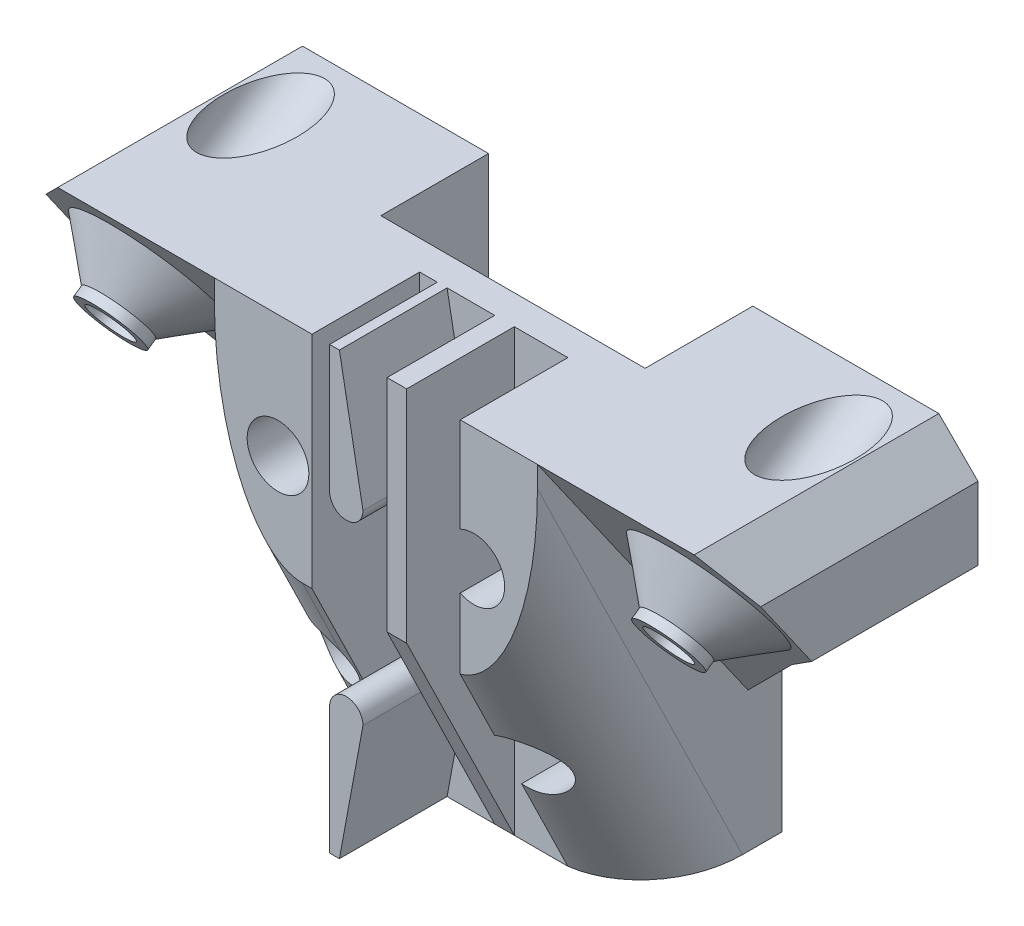
SolidWorks part; units mm, degrees
other "Markup1"
sketch "Sketch5" plane through (36.5, -22.5, 25) normal (0.516, -0.1626, 0.841) x (0.8506, -0.0189, -0.5255)
ref_plane "Front Plane" through (0, 0, 0) normal (0, 0, 1) x (1, 0, 0)
ref_plane "Top Plane" through (0, 0, 0) normal (0, 1, 0) x (1, 0, 0)
ref_plane "Right Plane" through (0, 0, 0) normal (1, 0, 0) x (0, 0, -1)
sketch "Sketch1" plane through (0, 0, 0) normal (0, 0, 1) x (1, 0, 0)
  line L1 (-16.5, -22.5) -> (16.5, -22.5)
  line L2 (-16.5, -22.5) -> (-16.5, 22.5)
  line L3 (-16.5, 22.5) -> (16.5, 22.5)
  line L4 (16.5, -22.5) -> (16.5, 22.5)
  line L5 (-16.5, -22.5) -> (16.5, 22.5) construction
  line L6 (-16.5, 22.5) -> (16.5, -22.5) construction
  point P0 (0, 0)
  dimension "D1" = 33
  dimension "D2" = 45
extrude "Boss-Extrude1" add sketch "Sketch1" along normal blind 14
sketch "Sketch4" plane through (-16.5, 0, 0) normal (-1, 0, 0) x (0, 0, 1)
  line L0 (25, 22.5) -> (14, 6.7904)
  line L1 (0, 22.5) -> (25, 22.5)
  line L2 (0, 22.5) -> (0, 6.7904)
  line L3 (0, 6.7904) -> (14, 6.7904)
  line L5 (14, 22.5) -> (14, -22.5) construction
  dimension "D1" = 25
  dimension "D2" = 55
extrude "Boss-Extrude2" add sketch "Sketch4" along normal blind 20 and the other way blind 53
sketch "Sketch6" plane through (0, -4.3439, 6.2037) normal (0, -0.5736, 0.8192) x (1, 0, 0)
  line L0 (-36.5, 23.1814) -> (36.5, 23.1814) construction
  line L1 (-36.5, 13.5924) -> (-36.5, 32.7703) construction
  line L2 (36.5, 13.5924) -> (36.5, 32.7703) construction
  circle A0 centre (-28.5, 23.1814) radius 2.3
  circle A1 centre (28.5, 23.1814) radius 2.3
  dimension "D1" = 4.6
  dimension "D2" = 8
  dimension "D3" = 8
extrude "Cut-Extrude3" cut sketch "Sketch6" against normal through all
sketch "Sketch2" plane through (0, 0, 0) normal (0, 0, 1) x (1, 0, 0)
  line L0 (36.5, 22.5) -> (-36.5, 22.5) construction
  line L1 (13.5, -22.5) -> (-13.5, -22.5)
  line L2 (13.5, -22.5) -> (13.5, 22.5)
  line L3 (13.5, 22.5) -> (-13.5, 22.5)
  line L4 (-13.5, -22.5) -> (-13.5, 22.5)
  line L5 (13.5, -22.5) -> (-13.5, 22.5) construction
  line L6 (13.5, 22.5) -> (-13.5, -22.5) construction
  line L7 (16.5, -22.5) -> (16.5, 6.7904) construction
  point P0 (0, 0)
  dimension "D1" = 3
extrude "Cut-Extrude1" cut sketch "Sketch2" along normal offset from surface (11 mm away) 3 up to face at (0, -7.8548, 14)
sketch "Sketch7" plane through (0, 0, 14) normal (0, 0, 1) x (1, 0, 0)
  line L0 (36.5, 22.5) -> (-36.5, 22.5) construction
  line L1 (-16.5, -22.5) -> (16.5, -22.5)
  line L2 (-16.5, -22.5) -> (-16.5, 22.5)
  line L3 (-16.5, 22.5) -> (16.5, 22.5)
  line L4 (16.5, -22.5) -> (16.5, 22.5)
  line L5 (16.5, -22.5) -> (16.5, 6.7904) construction
extrude "Boss-Extrude3" add sketch "Sketch7" along normal blind 11
chamfer "Chamfer1" distance 15 angle 45 2 edges at (16.5, 6.7904, 7) (-16.5, 6.7904, 7)
sketch "Sketch3" plane through (0, 0, 11) normal (0, 0, 1) x (1, 0, 0)
  line L1 (-10, -10) -> (10, -10) construction
  line L2 (-10, -10) -> (-10, 10) construction
  line L3 (-10, 10) -> (10, 10) construction
  line L4 (10, -10) -> (10, 10) construction
  line L5 (-10, -10) -> (10, 10) construction
  line L6 (-10, 10) -> (10, -10) construction
  circle A0 centre (-10, 10) radius 1.85
  circle A1 centre (10, 10) radius 1.85
  circle A2 centre (10, -10) radius 1.85
  circle A3 centre (-10, -10) radius 1.85
  point P0 (0, 0)
  dimension "D3" = 3.7
  dimension "D1" = 20
  dimension "D2" = 20
extrude "Cut-Extrude2" cut sketch "Sketch3" against normal through all both and the other way through all
sketch "Sketch8" plane through (0, 0, 25) normal (0, 0, 1) x (1, 0, 0)
  line L0 (16.5, 22.5) -> (-16.5, 22.5) construction
  line L1 (-6.53, 22.5) -> (-4.73, 22.5)
  line L2 (-6.53, 22.5) -> (-6.53, -22.5)
  line L3 (-6.53, -22.5) -> (-4.73, -22.5)
  line L4 (-4.73, 22.5) -> (-4.73, -22.5)
  line L5 (-16.5, -22.5) -> (16.5, -22.5) construction
  line L7 (3.14, 22.5) -> (8.61, 22.5)
  line L8 (3.14, 22.5) -> (3.14, -22.5)
  line L9 (3.14, -22.5) -> (8.61, -22.5)
  line L10 (8.61, 22.5) -> (8.61, -22.5)
  dimension "D1" = 4.73
  dimension "D2" = 3.14
  dimension "D3" = 1.8
  dimension "D4" = 5.47
extrude "Cut-Extrude4" cut sketch "Sketch8" against normal offset from surface (11 mm away) 3 up to face at (-11.85, -10, 11)
sketch "Sketch9" plane through (0, 0, 25) normal (0, 0, 1) x (1, 0, 0)
  line L4 (3.14, 22.5) -> (3.14, -22.5) construction
  line L5 (-4.73, -22.5) -> (1.14, -22.5)
  line L6 (-4.73, -22.5) -> (-4.73, 22.5)
  line L8 (1.14, -22.5) -> (1.14, 22.5)
  line L9 (-4.73, -22.5) -> (-4.73, 22.5) construction
  line L10 (-4.73, 22.5) -> (1.14, 22.5)
  dimension "D1" = 2
extrude "Cut-Extrude5" cut sketch "Sketch9" against normal up to surface (11 mm away) up to face at (-5.63, 0, 14)
ref_plane "Plane1" through (0, 0, 14) normal (0, 0, 1) x (1, 0, 0)
sketch "Sketch12" plane through (3.14, 0, 0) normal (1, 0, 0) x (0, 0, -1)
  line L0 (-14, -22.5) -> (-25, 0)
  line L1 (-14, 28.8039) -> (-14, -28.8039) construction
  line L2 (-25, -22.5) -> (-25, 22.5) construction
  line L5 (-25, -22.5) -> (0, -22.5) construction
  line L6 (-14, -22.5) -> (-25, -22.5)
  line L7 (-25, -22.5) -> (-25, 0)
extrude "Cut-Extrude7" cut sketch "Sketch12" along normal blind 25 and the other way blind 25
fillet "Fillet3" radius 9 2 edges at (16.5, -11.25, 19.5) (-16.5, -11.25, 19.5)
sketch "Sketch10" plane through (0, 0, 14) normal (0, 0, 1) x (1, 0, 0)
  line L0 (-4.73, -22.5) -> (-4.73, -9.5)
  line L1 (-6.53, -22.5) -> (1.14, -22.5) construction
  line L2 (-1.3211, -9.5) -> (-3.73, -22.5)
  line L3 (-3.73, -22.5) -> (-4.73, -22.5)
  arc A0 (-4.73, -9.5) -> (-1.3211, -9.5) centre (-3.0255, -9.5) cw
  dimension "D1" = 1
  dimension "D2" = 13
  dimension "D3" = 4.73
extrude "Boss-Extrude4" add sketch "Sketch10" along normal up to surface (11 mm away) up to face at (-8.15, 10, 25)
mirror "Mirror1" about plane through (0, 0, 0) normal (0, 1, 0) of "Boss-Extrude4"
sketch "Sketch13" plane through (0, 0, 14) normal (0, 0, 1) x (1, 0, 0)
  circle A0 centre (10, 10) radius 3.15
  circle A1 centre (10, -10) radius 3.15
  circle A2 centre (-10, -10) radius 3.15
  circle A3 centre (-10, 10) radius 3.15
  dimension "D1" = 6.3
extrude "Cut-Extrude8" cut sketch "Sketch13" along normal through all
sketch "Sketch14" plane through (0, -4.3439, 6.2037) normal (0, -0.5736, 0.8192) x (1, 0, 0)
  circle A0 centre (-28.5, 23.1814) radius 3.3
  circle A1 centre (-28.5, 23.1814) radius 2.3
  circle A2 centre (28.5, 23.1814) radius 2.3
  circle A3 centre (28.5, 23.1814) radius 3.3
  dimension "D1" = 1
extrude "Boss-Extrude5" add sketch "Sketch14" along normal blind 5
ref_plane "Plane2" through (0, -3.7703, 5.3846) normal (0, -0.5736, 0.8192) x (1, 0, 0)
sketch "Sketch15" plane through (0, -3.7703, 5.3846) normal (0, -0.5736, 0.8192) x (1, 0, 0)
  circle A0 centre (-28.5, 23.1814) radius 3.75
  circle A1 centre (28.5, 23.1814) radius 3.75
  dimension "D1" = 7.5
extrude "Cut-Extrude9" cut sketch "Sketch15" against normal through all
chamfer "Chamfer2" distance 4 angle 45 2 edges at (36.5, 22.5, 12.5) (-36.5, 22.5, 12.5)
sketch "Sketch16" plane through (0, 0, 0) normal (0, 0, -1) x (-1, 0, 0)
  line L0 (31.5, 6.7904) -> (36.5, 12.6452)
  line L1 (36.5, 18.5) -> (36.5, 6.7904) construction
  line L2 (36.5, 12.6452) -> (36.5, 6.7904)
  line L3 (36.5, 6.7904) -> (31.5, 6.7904)
  line L4 (-31.5, 6.7904) -> (-36.5, 11.0604)
  line L5 (-36.5, 18.5) -> (-36.5, 6.7904) construction
  line L6 (-36.5, 11.0604) -> (-36.5, 6.7904)
  line L7 (-36.5, 6.7904) -> (-31.5, 6.7904)
extrude "Cut-Extrude10" cut sketch "Sketch16" against normal through all
chamfer "Chamfer3" distance 4 angle 45 2 edges at (28.5, 11.942, 17.6072) (-28.5, 11.942, 17.6072)
